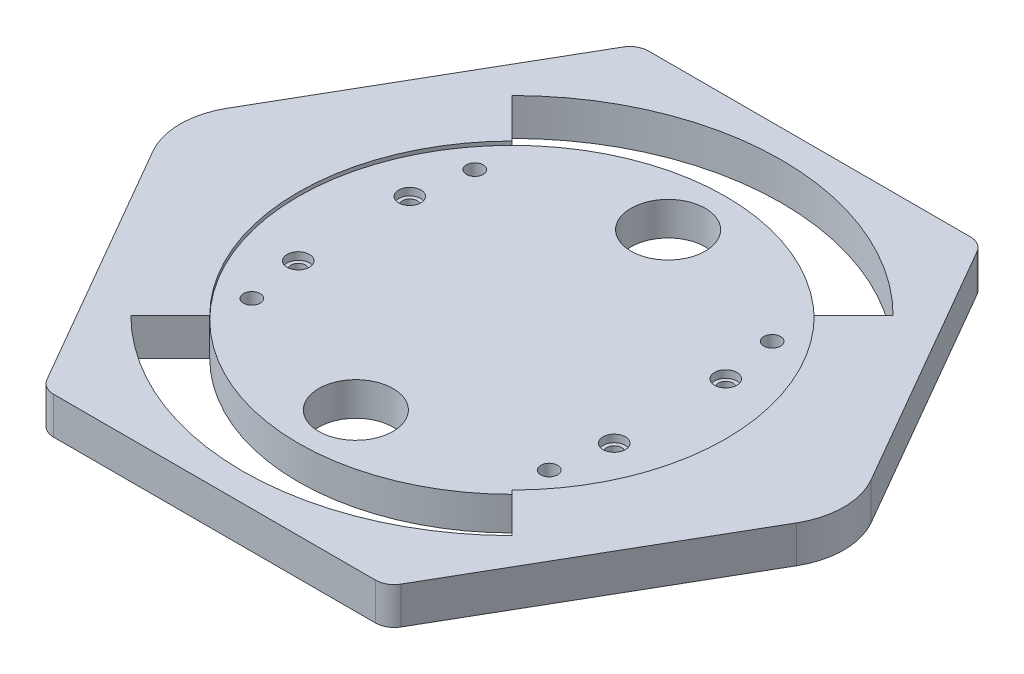
SolidWorks part; units mm, degrees
ref_plane "Front Plane" through (0, 0, 0) normal (0, 0, 1) x (1, 0, 0)
ref_plane "Top Plane" through (0, 0, 0) normal (0, 1, 0) x (1, 0, 0)
ref_plane "Right Plane" through (0, 0, 0) normal (1, 0, 0) x (0, 0, -1)
sketch "Sketch1" plane through (0, 0, 0) normal (0, 1, 0) x (1, 0, 0)
  line L1 (92.376, 0) -> (46.188, 80)
  line L2 (46.188, 80) -> (-46.188, 80)
  line L3 (-46.188, 80) -> (-92.376, 0)
  line L4 (-92.376, 0) -> (-46.188, -80)
  line L5 (-46.188, -80) -> (46.188, -80)
  line L6 (46.188, -80) -> (92.376, 0)
  circle A0 centre (0, 0) radius 80 construction
  dimension "D1" = 160
extrude "Boss-Extrude1" add sketch "Sketch1" along normal blind 10
sketch "Sketch8" plane through (0, 10, 0) normal (0, 1, 0) x (1, 0, 0)
  line L0 (-46.188, 80) -> (-92.376, 0) construction
  circle A0 centre (-42.5, 15) radius 2
  circle A1 centre (-42.5, -15) radius 2
  circle A2 centre (42.5, 15) radius 2
  circle A3 centre (42.5, -15) radius 2
  circle A4 centre (0, 0) radius 80 construction
  point P10 (0, 0)
  dimension "D1" = 30
  dimension "D3" = 4
  dimension "D4" = 42.5
  dimension "D5" = 15
  dimension "D2" = 85
extrude "Cut-Extrude10" cut sketch "Sketch8" against normal blind 21
sketch "Sketch10" plane through (0, 10, 0) normal (0, 1, 0) x (1, 0, 0)
  circle A0 centre (-42.5, 15) radius 3
  circle A1 centre (-42.5, -15) radius 3
  circle A2 centre (42.5, 15) radius 3
  circle A3 centre (42.5, -15) radius 3
  dimension "D1" = 6
extrude "Cut-Extrude11" cut sketch "Sketch10" against normal blind 3
sketch "Sketch11" plane through (0, 10, 0) normal (0, 1, 0) x (1, 0, 0)
  line L1 (46.188, 80) -> (-46.188, 80) construction
  circle A0 centre (-40, 30) radius 2.25
  circle A1 centre (-40, -30) radius 2.25
  circle A2 centre (40, -30) radius 2.25
  circle A3 centre (40, 30) radius 2.25
  circle A4 centre (0, 0) radius 80 construction
  dimension "D1" = 4.5
  dimension "D4" = 40
  dimension "D2" = 80
  dimension "D3" = 60
  dimension "D5" = 30
extrude "Cut-Extrude12" cut sketch "Sketch11" against normal blind 12
sketch "Sketch20" plane through (0, 10, 0) normal (0, 1, 0) x (1, 0, 0)
  line L0 (-46.188, 80) -> (-92.376, 0) construction
  line L1 (-51.2652, 51.2652) -> (0, 0) construction
  line L2 (0, 0) -> (51.2652, 51.2652) construction
  line L3 (0, 0) -> (-51.2652, -51.2652) construction
  line L4 (0, 0) -> (51.2652, -51.2652) construction
  line L5 (-40.6586, 40.6586) -> (-51.2652, 51.2652)
  line L6 (0, 0) -> (0, 72.5) construction
  line L7 (40.6586, -40.6586) -> (51.2652, -51.2652)
  line L9 (-40.6586, -40.6586) -> (-51.2652, -51.2652)
  line L11 (40.6586, 40.6586) -> (51.2652, 51.2652)
  circle A0 centre (0, 0) radius 57.5
  circle A1 centre (0, 0) radius 72.5
  circle A2 centre (0, 0) radius 80 construction
  circle M1 centre (40, 30) radius 2.25
  circle M2 centre (40, -30) radius 2.25
  circle M3 centre (-40, -30) radius 2.25
  circle M4 centre (-40, 30) radius 2.25
  circle M5 centre (42.5, -15) radius 3
  circle M6 centre (42.5, 15) radius 3
  circle M7 centre (-42.5, -15) radius 3
  circle M8 centre (-42.5, 15) radius 3
  dimension "D1" = 115
  dimension "D2" = 145
  dimension "D3" = 90
  dimension "D4" = 90
  dimension "D5" = 45
extrude "Cut-Extrude20" cut sketch "Sketch20" against normal blind 1 contours A0 M1 M3 M5 M7 M8 M6 M4 M2 region at (0, 10, 0)
extrude "Cut-Extrude23" cut sketch "Sketch20<7>" against normal blind 153 contours L11 A1 L5 A0 | L9 A1 L7 A0 region at (0, 10, -58.7803) region at (0, 10, 58.7803)
sketch "Sketch20<7>" plane through (0, 10, 0) normal (0, 1, 0) x (1, 0, 0) same geometry as "Sketch20"
sketch "Sketch27" plane through (0, 9, 0) normal (0, 1, 0) x (1, 0, 0)
  line L0 (0, 42) -> (0, -42) construction
  circle A0 centre (0, -42) radius 10
  circle A1 centre (0, 42) radius 10
  arc A3 (40.6586, 40.6586) -> (-40.6586, 40.6586) centre (0, 0) ccw construction
  circle A4 centre (0, 0) radius 57.5 construction
  dimension "D1" = 42
  dimension "D3" = 20
  dimension "D2" = 42
extrude "Cut-Extrude24" cut sketch "Sketch27" against normal blind 153
fillet "Fillet8" radius 20 2 edges at (-92.376, 5, 0) (92.376, 5, 0)
fillet "Fillet9" radius 5 4 edges at (-46.188, 5, 80) (46.188, 5, 80) (-46.188, 5, -80) (46.188, 5, -80)
